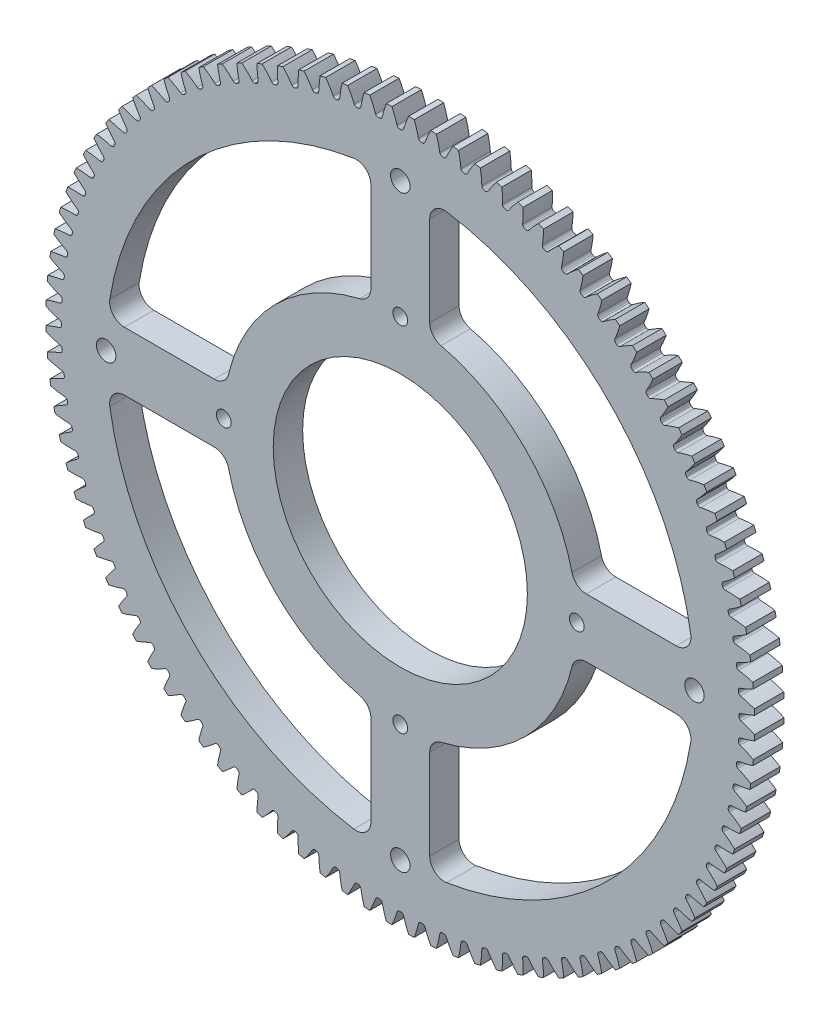
SolidWorks part; units mm, degrees
material "Delrin 2700 NC010, Low Viscosity Acetal Copolymer (SS)"
ref_plane "Front Plane" through (0, 0, 0) normal (0, 0, 1) x (1, 0, 0)
ref_plane "Top Plane" through (0, 0, 0) normal (0, 1, 0) x (1, 0, 0)
ref_plane "Right Plane" through (0, 0, 0) normal (1, 0, 0) x (0, 0, -1)
sketch "Sketch1" plane through (0, 0, 0) normal (0, 0, 1) x (1, 0, 0)
  line L0 (0, 0) -> (0, 75) construction
  line L1 (-24.1045, 83.7733) -> (24.1045, 66.2267) construction
  circle A0 centre (0, 0) radius 73.125 construction
  circle A1 centre (0, 0) radius 76.5 construction
  circle A2 centre (0, 0) radius 75 construction
  circle A3 centre (0, 0) radius 70.4769 construction
  circle A4 centre (0, 0) radius 40 construction
  circle A5 centre (0, 0) radius 7.5 construction
  point P8 (0.75, 0)
  point P13 (50, 0)
  dimension "OD" = 153
  dimension "Root Diameter" = 146.25
  dimension "Gear Pitch Diameter" = 150
  dimension "Base Diameter" = 140.9539
  dimension "Hub Diameter" = 80
  dimension "For Shaft Diameter" = 15
  dimension "Pressure Angle" = 20
  dimension "Number of Teeth" = 100
  dimension "Module" = 1.5
sketch "Sketch2" plane through (0, 0, 0) normal (1, 0, 0) x (0, 0, -1)
  line L0 (-14, 0) -> (6.35, 0) construction
  line L1 (6.35, 76.5) -> (6.35, -76.5) construction
  line L2 (0, -40) -> (-14, -40) construction
  line L3 (-14, 76.5) -> (6.35, 76.5) construction
  line L8 (-14, -40) -> (-14, 40) construction
  point P4 (0, 76.5)
  point P5 (-7, 0)
  dimension "Overall Width" = 20.35
  dimension "Hub Width" = 14
  dimension "Approx Set Screw Positon" = 7
  dimension "Face Width" = 6.35
sketch "Sketch3" plane through (0, 0, 0) normal (0, 0, 1) x (1, 0, 0)
  circle A0 centre (0, 0) radius 76.5
  circle A1 centre (0, 0) radius 76.5 construction
extrude "Boss-Extrude1" add sketch "Sketch3" against normal up to vertex (6.35 mm away) up to point (0, 0, -6.35)
sketch "Sketch4" plane through (0, 0, 0) normal (0, 0, 1) x (1, 0, 0)
  line L0 (73.1226, 0.589) -> (73.1226, -0.589)
  arc A3 (76.4789, 1.7978) -> (76.4789, -1.7978) centre (0, 0) cw
  circle A4 centre (0, 0) radius 76.5 construction
  arc A5 (73.1226, 0.589) -> (76.4789, 1.7978) centre (66.9977, 22.8603) ccw
  circle A8 centre (0, 0) radius 73.125 construction
  arc A9 (73.1226, -0.589) -> (76.4789, -1.7978) centre (66.9977, -22.8603) cw
  spline S0 degree 4 poles (70.4769, 0.0566) (70.4862, 0.0567) (70.5123, 0.0572) (70.5615, 0.0592) (70.6419, 0.0639) (70.7443, 0.072) (70.8767, 0.0848) (71.0327, 0.1031) (71.2042, 0.1265) (71.3909, 0.1556) (71.5772, 0.1877) (71.763, 0.2226) (71.9483, 0.2601) (72.1727, 0.3086) (72.4418, 0.3712) (72.7566, 0.4506) (73.1136, 0.5483) (73.4778, 0.6559) (73.8362, 0.7684) (74.1986, 0.8897) (74.5493, 1.0125) (74.9138, 1.148) (75.2504, 1.277) (75.6277, 1.4303) (75.9323, 1.5566) (76.3344, 1.7325) (76.572, 1.8392) (76.8501, 1.9673) (76.9736, 2.0258) (77.0497, 2.0619) knots 0 0 0 0 0 0.005377 0.015084 0.028532 0.04661 0.064855 0.092111 0.119476 0.146842 0.174209 0.201575 0.228941 0.256307 0.307035 0.361767 0.4165 0.471232 0.525964 0.580697 0.635429 0.690161 0.744894 0.799626 0.854358 0.909091 0.954545 1 1 1 1 1 construction
  spline S1 degree 4 poles (70.4769, 0.0566) (70.4862, 0.0567) (70.5123, 0.0572) (70.5615, 0.0592) (70.6419, 0.0639) (70.7443, 0.072) (70.8767, 0.0848) (71.0327, 0.1031) (71.2042, 0.1265) (71.3909, 0.1556) (71.5772, 0.1877) (71.763, 0.2226) (71.9483, 0.2601) (72.1727, 0.3086) (72.4418, 0.3712) (72.7566, 0.4506) (73.1136, 0.5483) (73.4778, 0.6559) (73.8362, 0.7684) (74.1986, 0.8897) (74.5493, 1.0125) (74.9138, 1.148) (75.2504, 1.277) (75.6277, 1.4303) (75.9323, 1.5566) (76.2472, 1.6943) (76.4005, 1.7625) (76.4789, 1.7978) knots 0 0 0 0 0 0.005377 0.015084 0.028532 0.04661 0.064855 0.092111 0.119476 0.146842 0.174209 0.201575 0.228941 0.256307 0.307035 0.361767 0.4165 0.471232 0.525964 0.580697 0.635429 0.690161 0.744894 0.799626 0.854358 0.909091 0.909091 0.909091 0.909091 0.909091 construction
  spline S2 degree 4 poles (70.4769, -0.0566) (70.4862, -0.0567) (70.5123, -0.0572) (70.5615, -0.0592) (70.6419, -0.0639) (70.7443, -0.072) (70.8767, -0.0848) (71.0327, -0.1031) (71.2042, -0.1265) (71.3909, -0.1556) (71.5772, -0.1877) (71.763, -0.2226) (71.9483, -0.2601) (72.1727, -0.3086) (72.4418, -0.3712) (72.7566, -0.4506) (73.1136, -0.5483) (73.4778, -0.6559) (73.8362, -0.7684) (74.1986, -0.8897) (74.5493, -1.0125) (74.9138, -1.148) (75.2504, -1.277) (75.6277, -1.4303) (75.9323, -1.5566) (76.3344, -1.7325) (76.572, -1.8392) (76.8501, -1.9673) (76.9736, -2.0258) (77.0497, -2.0619) knots 0 0 0 0 0 0.005377 0.015084 0.028532 0.04661 0.064855 0.092111 0.119476 0.146842 0.174209 0.201575 0.228941 0.256307 0.307035 0.361767 0.4165 0.471232 0.525964 0.580697 0.635429 0.690161 0.744894 0.799626 0.854358 0.909091 0.954545 1 1 1 1 1 construction
  spline S3 degree 4 poles (70.4769, -0.0566) (70.4862, -0.0567) (70.5123, -0.0572) (70.5615, -0.0592) (70.6419, -0.0639) (70.7443, -0.072) (70.8767, -0.0848) (71.0327, -0.1031) (71.2042, -0.1265) (71.3909, -0.1556) (71.5772, -0.1877) (71.763, -0.2226) (71.9483, -0.2601) (72.1727, -0.3086) (72.4418, -0.3712) (72.7566, -0.4506) (73.1136, -0.5483) (73.4778, -0.6559) (73.8362, -0.7684) (74.1986, -0.8897) (74.5493, -1.0125) (74.9138, -1.148) (75.2504, -1.277) (75.6277, -1.4303) (75.9323, -1.5566) (76.2472, -1.6943) (76.4005, -1.7625) (76.4789, -1.7978) knots 0 0 0 0 0 0.005377 0.015084 0.028532 0.04661 0.064855 0.092111 0.119476 0.146842 0.174209 0.201575 0.228941 0.256307 0.307035 0.361767 0.4165 0.471232 0.525964 0.580697 0.635429 0.690161 0.744894 0.799626 0.854358 0.909091 0.909091 0.909091 0.909091 0.909091 construction
  dimension "D1" = 1.1781
extrude "Cut-Extrude1" cut sketch "Sketch4" against normal through all both and the other way through all
fillet "Fillet1" radius 0.589 2 edges at (73.1226, 0.589, -3.175) (73.1226, -0.589, -3.175)
pattern_circular "CirPattern1" count 100 over 360 about axis through (0, 0, 14) along (0, 0, -1) of "Cut-Extrude1", "Fillet1"
sketch "Sketch6" plane through (0, 0, -6.35) normal (0, 0, -1) x (-1, 0, 0)
  circle A0 centre (63.5, 0) radius 2.1
  circle A4 centre (38.1, 0) radius 1.6
  circle A5 centre (0, -63.5) radius 2.1
  circle A6 centre (0, -38.1) radius 1.6
  circle A7 centre (-63.5, 0) radius 2.1
  circle A8 centre (-38.1, 0) radius 1.6
  circle A9 centre (0, 63.5) radius 2.1
  circle A10 centre (0, 38.1) radius 1.6
  point P24 (0, 0)
  dimension "D1" = 4.2
  dimension "D5" = 3.2
  dimension "D3" = 63.5
  dimension "D2" = 38.1
  dimension "D4" = 4
extrude "Cut-Extrude3" cut sketch "Sketch6" against normal through all
sketch "Sketch7" plane through (0, 0, 0) normal (0, 0, 1) x (1, 0, 0)
  circle A0 centre (0, 0) radius 75 construction
  dimension "D1" = 150
sketch "Sketch10" plane through (0, 0, -6.35) normal (0, 0, -1) x (-1, 0, 0)
  circle A0 centre (0, 0) radius 27.432
  dimension "D1" = 54.864
extrude "Cut-Extrude4" cut sketch "Sketch10" against normal through all
sketch "Sketch11" plane through (0, 0, -6.35) normal (0, 0, -1) x (-1, 0, 0)
  line L0 (6.35, 37.5671) -> (6.35, 63.1817)
  line L1 (37.5671, 6.35) -> (63.1817, 6.35)
  arc A0 (37.5671, 6.35) -> (6.35, 37.5671) centre (0, 0) ccw
  arc A1 (63.1817, 6.35) -> (6.35, 63.1817) centre (0, 0) ccw
  dimension "D1" = 6.35
  dimension "D2" = 6.35
extrude "Cut-Extrude5" cut sketch "Sketch11" against normal through all
fillet "Fillet3" radius 3.175 4 edges at (-37.5671, 6.35, -3.175) (-63.1817, 6.35, -3.175) (-6.35, 37.5671, -3.175) (-6.35, 63.1817, -3.175)
pattern_circular "CirPattern3" count 4 over 360 about axis through (0, 0, -6.35) along (0, 0, -1) of "Cut-Extrude5", "Fillet3"
sketch "Sketch12" plane through (0, 0, 0) normal (0, 0, 1) x (1, 0, 0)
  circle A0 centre (0, 38.1) radius 3
  circle A1 centre (38.1, 0) radius 3
  circle A2 centre (-38.1, 0) radius 3
  circle A3 centre (0, -38.1) radius 3
  dimension "D1" = 6
extrude "Cut-Extrude6" cut sketch "Sketch12" along normal blind 3 from surface starting at face at (30.3415, 30.3415, -6.35)
equation "\"Number of Teeth\"= 100"
equation "\"Module\"= 1.5"
equation "\"Diametral Pitch\"= 1 / \"Module\""
equation "\"Dedendum\"= 1.25 / \"Diametral Pitch\""
equation "\"Pitch Diameter\"= \"Module\" * \"Number of Teeth\""
equation "\"Root Diameter\"= \"Pitch Diameter\" - ( 2 * \"Dedendum\" )"
equation "\"Root Diameter@Sketch1\"=\"Root Diameter\""
equation "\"OD@Sketch1\" = \"Outside Diameter\""
equation "\"D1@CirPattern1\"=\"Number of Teeth\""
equation "\"Pressure Angle\"=20"
equation "\"Base Diameter\"= \"Pitch Diameter\" * cos ( \"Pressure Angle\" )"
equation "\"Outside Diameter\"= ( \"Number of Teeth\" + 2 ) / \"Diametral Pitch\""
equation "\"Pitch Angle\"= 360deg / \"Number of Teeth\""
equation "\"Alpha\"= sqr ( \"Pitch Diameter\" ^ 2 - \"Base Diameter\" ^ 2 ) / \"Base Diameter\" * 180 / PI - \"Pressure Angle\""
equation "\"Beta\"= ( \"Pitch Angle\" / 4 - \"Alpha\" )"
equation "\"Phi\"= sqr ( ( \"Outside Diameter\" / 2 ) ^ 2 - ( \"Base Diameter\" / 2 ) ^ 2 ) / ( \"Base Diameter\" / 2 )"
equation "\"Addendum\"= 1 / \"Diametral Pitch\""
equation "\"WorkingDepth\"= 2 / \"Diametral Pitch\""
equation "\"WholeDepth\"= 2.25 / \"Diametral Pitch\""
equation "\"Clearance\"= 0.25 / \"Diametral Pitch\""
equation "\"ToothThickness\"= ( pi * 2 ) / \"Diametral Pitch\""
equation "\"CircularPitch\"= pi / \"Diametral Pitch\""
equation "\"Number of Teeth@Sketch1\"=\"Number of Teeth\""
equation "\"Module@Sketch1\"=\"Module\""
equation "\"Pressure Angle@Sketch1\"=\"Pressure Angle\""
equation "\"Gear Pitch Diameter@Sketch1\"=\"Pitch Diameter\""
equation "\"Base Diameter@Sketch1\"=\"Base Diameter\""
equation "\"Fillet\"= \"Clearance\" * cos ( \"Pressure Angle\" ) * tan ( ( 90 + \"Pressure Angle\" ) / 2 )"
equation "\"D1\"= \"Fillet\""
equation "\"Approx Set Screw Positon@Sketch2\" = \"Hub Width@Sketch2\" / 2"
equation "\"D2\"= \"Fillet\" * 2"
equation "\"D1@Sketch4\"=\"CircularPitch\"*0.25"
equation "\"D1@Fillet1\"=\"CircularPitch\"*0.125"
equation "\"Overall Width@Sketch2\"=14+0.25in"
equation "\"D1@Sketch10\"=2.16in"
equation "\"D1@Sketch11\"=0.25in"
equation "\"D2@Sketch11\"=0.25in"
equation "\"D1@Fillet3\"=0.125in"
